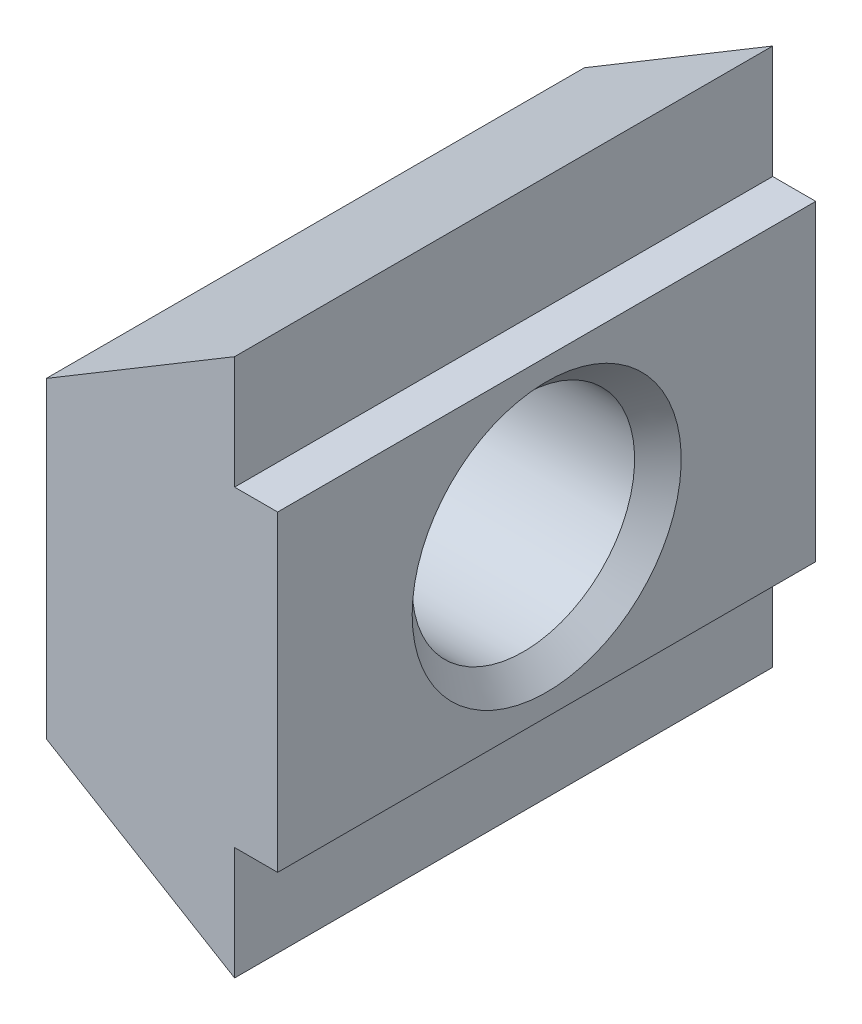
SolidWorks part; units mm, degrees
ref_plane "Front Plane" through (0, 0, 0) normal (0, 0, 1) x (1, 0, 0)
ref_plane "Top Plane" through (0, 0, 0) normal (0, 1, 0) x (1, 0, 0)
ref_plane "Right Plane" through (0, 0, 0) normal (1, 0, 0) x (0, 0, -1)
ref_plane "Plane1" through (0, 0, 0) normal (0, 0, 1) x (1, 0, 0)
sketch "Sketch1" plane through (0, 0, 0) normal (0, 0, 1) x (1, 0, 0)
  line L0 (-4.3, 2.9) -> (-4.3, -2.9)
  line L1 (-4.3, -2.9) -> (-0.8, -5)
  line L2 (-0.8, -5) -> (-0.8, -2.9)
  line L3 (-0.8, -2.9) -> (0, -2.9)
  line L4 (0, -2.9) -> (0, 2.9)
  line L5 (0, 2.9) -> (-0.8, 2.9)
  line L6 (-0.8, 2.9) -> (-0.8, 5)
  line L7 (-0.8, 5) -> (-4.3, 2.9)
extrude "Boss-Extrude1" add sketch "Sketch1" against normal blind 5 and the other way blind 5
ref_plane "Plane2" through (0, 0, 0) normal (0, 0, 1) x (1, 0, 0)
sketch "Sketch2" plane through (0, 0, 0) normal (0, 0, 1) x (1, 0, 0)
  line L0 (-4.3, 0) -> (-4.3, 2.5)
  line L1 (-4.3, 2.5) -> (-3.867, 2.067)
  line L2 (-3.867, 2.067) -> (-0.433, 2.067)
  line L3 (-0.433, 2.067) -> (0, 2.5)
  line L4 (0, 2.5) -> (0, 0)
  line L5 (0, 0) -> (-4.3, 0)
  line L6 (0, 0) -> (-4.3, 0) construction
revolve "Cut-Revolve1" cut sketch "Sketch2" angle 360 about L6 reverse direction yes
cosmetic thread "Cosmetic Thread1" parameters "D1"=4.3, "D2"=5
